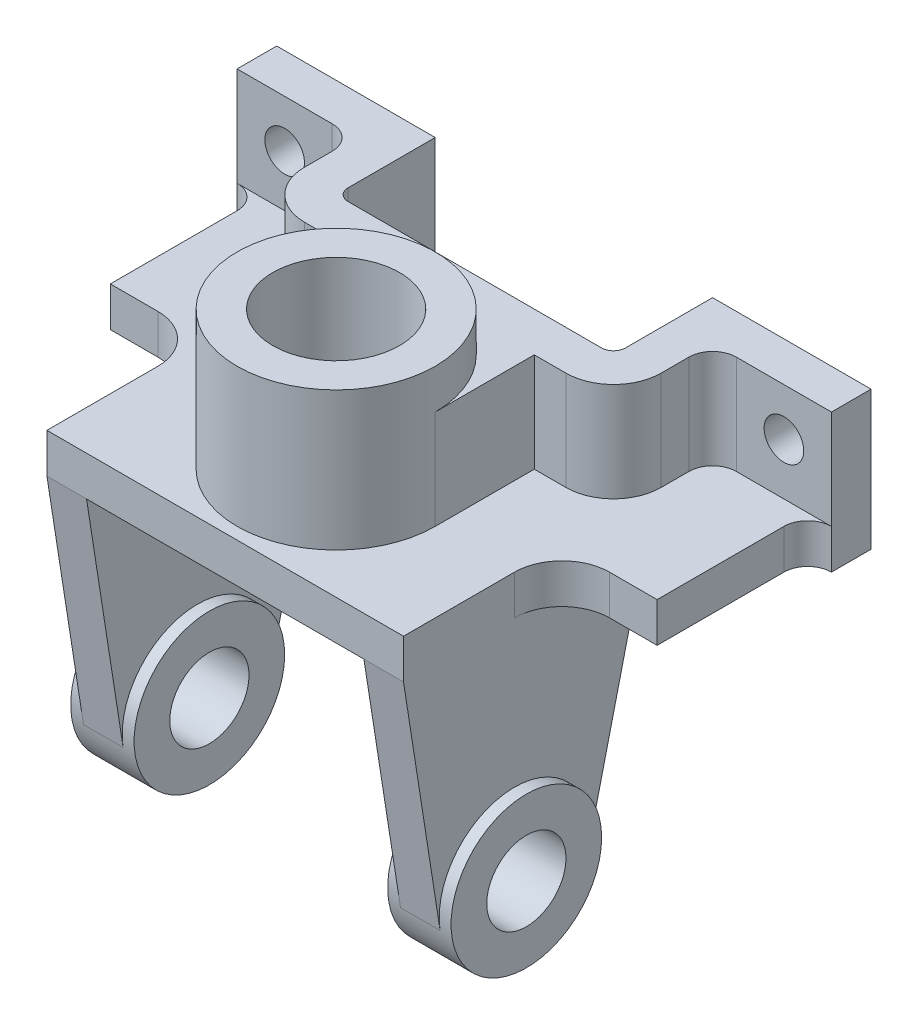
SolidWorks part; units mm, degrees
ref_plane "前视基准面" through (0, 0, 0) normal (0, 0, 1) x (1, 0, 0)
ref_plane "上视基准面" through (0, 0, 0) normal (0, 1, 0) x (1, 0, 0)
ref_plane "右视基准面" through (0, 0, 0) normal (1, 0, 0) x (0, 0, -1)
other "Configuration Table"
sketch "草图1" plane through (0, 0, 0) normal (0, 1, 0) x (1, 0, 0)
  line L0 (-71.7073, 0) -> (90.3659, 0) construction
  line L1 (0, 130.4807) -> (0, -67.9268) construction
  line L3 (45, 0) -> (45, 40)
  line L4 (45, 40) -> (69, 40)
  line L5 (69, 40) -> (69, 78)
  line L10 (69, 78) -> (75, 78)
  line L11 (75, 78) -> (75, 88)
  line L12 (75, 88) -> (-75, 88)
  line L13 (-45, 0) -> (45, 0)
  line L15 (-75, 78) -> (-75, 88)
  line L16 (-69, 78) -> (-75, 78)
  line L17 (-69, 40) -> (-69, 78)
  line L18 (-45, 40) -> (-69, 40)
  line L19 (-45, 0) -> (-45, 40)
  point P7 (0, 0)
  point P13 (0, 88)
  point P14 (0, 0)
  point P16 (0, 88)
  dimension "D1" = 45
  dimension "D2" = 40
  dimension "D3" = 69
  dimension "D4" = 10
  dimension "D5" = 6
  dimension "D6" = 38
extrude "凸台-拉伸1" add sketch "草图1" against normal blind 10
fillet "圆角1" radius 12 2 edges at (45, -5, -40) (-45, -5, -40)
fillet "圆角2" radius 6 2 edges at (69, -5, -78) (-69, -5, -78)
sketch "草图2" plane through (0, 0, 0) normal (0, 1, 0) x (1, 0, 0)
  line L0 (75, 88) -> (-75, 88) construction
  line L1 (0, 0) -> (0, 63) construction
  line L2 (-75, 88) -> (-35, 88)
  line L3 (-35, 88) -> (-35, 63)
  line L4 (-35, 63) -> (35, 63)
  line L5 (-75, 78) -> (-45, 78)
  line L6 (-45, 78) -> (-45, 53)
  line L7 (-45, 53) -> (-25, 53)
  line L8 (-25, 28) -> (-25, 53)
  line L9 (25, 28) -> (25, 53)
  line L10 (45, 53) -> (25, 53)
  line L11 (45, 78) -> (45, 53)
  line L12 (75, 78) -> (45, 78)
  line L13 (35, 88) -> (35, 63)
  line L14 (75, 88) -> (35, 88)
  line L15 (-75, 88) -> (-75, 78)
  line L16 (75, 88) -> (75, 78)
  circle A0 centre (0, 28) radius 16
  circle A1 centre (0, 28) radius 25
  line M10 (75, 78) -> (75, 88)
  line M11 (75, 88) -> (-75, 88)
  line M12 (-75, 88) -> (-75, 78)
  dimension "D1" = 32
  dimension "D2" = 50
  dimension "D3" = 60
  dimension "D4" = 70
  dimension "D5" = 90
  dimension "D6" = 10
  dimension "D7" = 25
extrude "凸台-拉伸2" add sketch "草图2" along normal blind 25 contours A1 L1 L4 L3 L5 L6 L7 L8 M11 M12 | L1 A1 L9 L10 L11 L12 L13 L4 M10 M11 region at (-35.9124, 0, -67.2189) region at (35.9124, 0, -67.2189)
extrude "凸台-拉伸3" add sketch "草图2<3>" along normal blind 35 contours L1 A1 A0 | A1 L1 A0 region at (-17.2824, 0, -10.7176) region at (0.559, 0, -7.5)
sketch "草图2<3>" plane through (0, 0, 0) normal (0, 1, 0) x (1, 0, 0) same geometry as "草图2"
extrude "切除-拉伸1" cut sketch "草图2<4>" against normal blind 35 contours L13 L3 L4 M11 region at (0, 0, -75.5)
sketch "草图2<4>" plane through (0, 0, 0) normal (0, 1, 0) x (1, 0, 0) same geometry as "草图2"
fillet "圆角3" radius 6 2 edges at (45, 12.5, -78) (-45, 12.5, -78)
fillet "圆角4" radius 12 2 edges at (45, 12.5, -53) (-45, 12.5, -53)
fillet "圆角5" radius 3 2 edges at (35, 7.5, -63) (-35, 7.5, -63)
extrude "切除-拉伸2" cut sketch "草图2<5>" against normal blind 35 contours A0 L1 | L1 A0 region at (-6.7906, 0, -28) region at (6.7906, 0, -28)
sketch "草图2<5>" plane through (0, 0, 0) normal (0, 1, 0) x (1, 0, 0) same geometry as "草图2"
sketch "草图6" plane through (0, 0, 0) normal (1, 0, 0) x (0, 0, -1)
  line L0 (9.2287, -68.9392) -> (0, -10)
  line L1 (46.4739, -70.44) -> (61, -10)
  line L2 (0, -10) -> (0, 0) construction
  line L3 (0, -10) -> (28, -10) construction
  line L4 (40, -10) -> (72, -10) construction
  line L5 (0, -10) -> (78, -10)
  line L6 (78, -10) -> (78, 0) construction
  circle A0 centre (28, -66) radius 19
  circle A1 centre (28, -66) radius 10
  arc A2 (56.4318, -29.0073) -> (78, -10) centre (80.7396, -34.8494) cw
  point P23 (61, -10)
  dimension "D1" = 38
  dimension "D2" = 20
  dimension "D6" = 25
  dimension "D3" = 28
  dimension "D4" = 56
  dimension "D5" = 33
extrude "凸台-拉伸4" add sketch "草图6" along normal blind 10 from offset 35 contours A0 L1 L5 L0 region at (0, -30.3309, -29.7789)
extrude "凸台-拉伸5" add sketch "草图6<4>" along normal blind 16 from offset 32 contours A0 A1 region at (0, -47.593, -26.5676)
sketch "草图6<4>" plane through (0, 0, 0) normal (1, 0, 0) x (0, 0, -1) same geometry as "草图6"
mirror "镜向1" about plane through (0, 0, 0) normal (1, 0, 0) of "凸台-拉伸5", "凸台-拉伸4"
sketch "草图7" plane through (0, 0, 0) normal (0, 0, 1) x (1, 0, 0)
  line L0 (-75, -10) -> (-69, -10) construction
  line L1 (-75, 25) -> (-75, 0) construction
  circle A0 centre (-63, 13) radius 5
  dimension "D1" = 23
  dimension "D3" = 10
  dimension "D2" = 12
extrude "切除-拉伸3" cut sketch "草图7" against normal through all
mirror "镜向2" about plane through (0, 0, 0) normal (1, 0, 0) of "切除-拉伸3"
